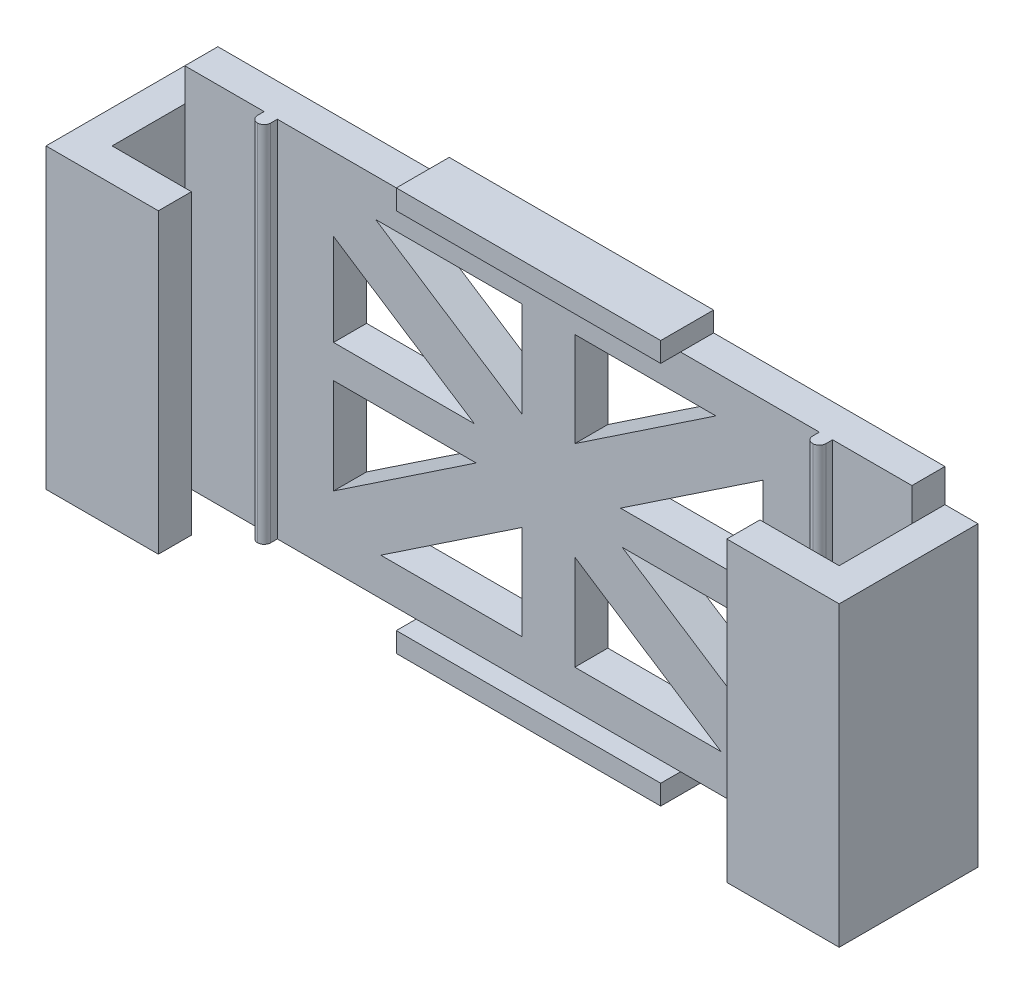
SolidWorks part; units mm, degrees
ref_plane "Front Plane" through (0, 0, 0) normal (0, 0, 1) x (1, 0, 0)
ref_plane "Top Plane" through (0, 0, 0) normal (0, 1, 0) x (1, 0, 0)
ref_plane "Right Plane" through (0, 0, 0) normal (1, 0, 0) x (0, 0, -1)
sketch "Sketch1" plane through (0, 0, 0) normal (0, 0, 1) x (1, 0, 0)
  line L0 (0, -36.5349) -> (0, 35.9982) construction
  line L1 (-55, -27.5) -> (55, -27.5)
  line L2 (-55, -27.5) -> (-55, 27.5)
  line L3 (-55, 27.5) -> (55, 27.5)
  line L4 (55, -27.5) -> (55, 27.5)
  line L5 (-55, -27.5) -> (55, 27.5) construction
  line L6 (-55, 27.5) -> (55, -27.5) construction
  line L11 (-43, -27.5) -> (-41, -27.5)
  line L12 (-43, -27.5) -> (-43, 27.5)
  line L13 (-43, 27.5) -> (-41, 27.5)
  line L14 (-41, -27.5) -> (-41, 27.5)
  line L15 (55, 27.5) -> (43, 27.5)
  line L16 (43, -27.5) -> (43, 27.5)
  line L17 (55, -27.5) -> (43, -27.5)
  line L18 (55, -27.5) -> (55, 27.5)
  line L19 (43, 27.5) -> (41, 27.5)
  line L20 (41, -27.5) -> (41, 27.5)
  line L21 (43, -27.5) -> (41, -27.5)
  line L22 (43, -27.5) -> (43, 27.5)
  point P0 (0, 0)
  dimension "D1" = 55
  dimension "D2" = 110
  dimension "D3" = 12
  dimension "D4" = 2
extrude "Boss-Extrude1" add sketch "Sketch1" along normal blind 5 contours L1 L20 L3 L14 | L1 L12 L3 L2 | L16 L1 L4 L3 region at (-49, 0, 0) region at (0, 0, 0) region at (49, 0, 0)
extrude "Boss-Extrude2" add sketch "Sketch1<3>" along normal blind 7 contours L20 L1 L16 L3 | L12 L13 L14 L11 region at (42, 0, 0)
sketch "Sketch1<3>" plane through (0, 0, 0) normal (0, 0, 1) x (1, 0, 0) same geometry as "Sketch1"
fillet "Fillet1" radius 1 4 edges at (-43, 0, 7) (-41, 0, 7) (41, 0, 7) (43, 0, 7)
sketch "Sketch2" plane through (0, 0, 0) normal (0, 0, 1) x (1, 0, 0)
  line L0 (-55, -27.5) -> (-55, 27.5) construction
  line L1 (-55, 22.5) -> (-60, 22.5)
  line L2 (-55, 22.5) -> (-55, -22.5)
  line L3 (-55, -22.5) -> (-60, -22.5)
  line L4 (-60, 22.5) -> (-60, -22.5)
  line L5 (-55, -27.5) -> (-43, -27.5) construction
  line L6 (-55, 27.5) -> (-43, 27.5) construction
  line L7 (0, -33.0129) -> (0, 33.9612) construction
  line L8 (55, -22.5) -> (60, -22.5)
  line L9 (60, 22.5) -> (60, -22.5)
  line L10 (55, 22.5) -> (60, 22.5)
  line L11 (55, 22.5) -> (55, -22.5)
  dimension "D1" = 5
  dimension "D2" = 5
  dimension "D3" = 5
extrude "Boss-Extrude3" add sketch "Sketch2" along normal blind 16
ref_plane "Plane1" through (0, 0, 16) normal (0, 0, 1) x (1, 0, 0)
sketch "Sketch3" plane through (0, 0, 16) normal (0, 0, 1) x (1, 0, 0)
  line L0 (0, 0) -> (0, -34.1454) construction
  line L1 (60, -22.5) -> (43, -22.5)
  line L2 (60, -22.5) -> (60, 22.5)
  line L3 (60, 22.5) -> (43, 22.5)
  line L4 (43, -22.5) -> (43, 22.5)
  line L5 (-60, 22.5) -> (-43, 22.5)
  line L6 (-43, -22.5) -> (-43, 22.5)
  line L7 (-60, -22.5) -> (-43, -22.5)
  line L8 (-60, -22.5) -> (-60, 22.5)
  dimension "D1" = 45
  dimension "D2" = 17
extrude "Boss-Extrude4" add sketch "Sketch3" along normal blind 5
sketch "Sketch4" plane through (0, 0, 0) normal (0, 0, 1) x (1, 0, 0)
  line L0 (-41, -27.5) -> (41, -27.5) construction
  line L1 (-20, -27.5) -> (20, -27.5)
  line L2 (0, -27.5) -> (0, -30.5)
  line L3 (-20, -30.5) -> (20, -30.5)
  line L4 (20, -27.5) -> (20, -30.5)
  line L5 (0, -13.7133) -> (0, 0) construction
  line L6 (0, 0) -> (14.001, 0) construction
  line L7 (-20, -27.5) -> (-20, -30.5)
  line L8 (-20, 27.5) -> (-20, 30.5)
  line L9 (-20, 27.5) -> (20, 27.5)
  line L10 (20, 27.5) -> (20, 30.5)
  line L11 (-20, 30.5) -> (20, 30.5)
  dimension "D1" = 3
  dimension "D2" = 20
extrude "Boss-Extrude5" add sketch "Sketch4" along normal blind 8 contours L4 L1 L2 L3 | L3 L4 L1 L7 | L9 L10 L11 L8 region at (10, -29, 0)
sketch "Sketch5" plane through (0, 0, 5) normal (0, 0, 1) x (1, 0, 0)
  line L0 (-41, 27.5) -> (41, -27.5)
  line L1 (-41, -27.5) -> (41, 27.5)
  line L2 (0, -27.5) -> (0, 27.5)
  line L3 (-20, -27.5) -> (20, -27.5) construction
  line L4 (-20, 27.5) -> (20, 27.5) construction
  line L5 (41, -27.5) -> (41, 27.5) construction
  line L6 (-41, -27.5) -> (-41, 27.5) construction
  line L7 (-41, 0) -> (41, 0)
  line L8 (41, -27.5) -> (41, 27.5) construction
  line L9 (-41, 2.5) -> (41, 2.5)
  line L10 (-41, 2.5) -> (-41, -2.5)
  line L11 (-41, -2.5) -> (41, -2.5)
  line L12 (41, 2.5) -> (41, -2.5)
  line L13 (-41, 2.5) -> (41, -2.5) construction
  line L14 (-41, -2.5) -> (41, 2.5) construction
  line L15 (-41, 21.92) -> (34.9082, -27.5)
  line L18 (-34.9082, 27.5) -> (41, -21.92)
  line L19 (-41, 22.2) -> (41, -22.2) construction
  line L20 (35.583, -27.5) -> (-35.583, 27.5) construction
  line L21 (-41, -22.6544) -> (33.8596, 27.5)
  line L24 (-33.8596, -27.5) -> (41, 22.6544)
  line L25 (-41, -22.9039) -> (41, 22.9039) construction
  line L26 (34.6299, 27.5) -> (-34.6299, -27.5) construction
  line L27 (-20, 27.5) -> (20, 27.5) construction
  line L28 (-4, -27.5) -> (4, -27.5)
  line L29 (-4, -27.5) -> (-4, 27.5)
  line L30 (-4, 27.5) -> (4, 27.5)
  line L31 (4, -27.5) -> (4, 27.5)
  line L32 (-4, -27.5) -> (4, 27.5) construction
  line L33 (-4, 27.5) -> (4, -27.5) construction
  line L35 (-41, -27.5) -> (41, -27.5)
  line L36 (-41, -27.5) -> (-41, 27.5)
  line L37 (-41, 27.5) -> (41, 27.5)
  line L38 (41, -27.5) -> (41, 27.5)
  line L39 (-41, -27.5) -> (41, 27.5) construction
  line L40 (-41, 27.5) -> (41, -27.5) construction
  line L41 (32.5, 21.7988) -> (-32.5, 21.7988)
  line L42 (32.5, 21.7988) -> (32.5, -21.7988)
  line L43 (32.5, -21.7988) -> (-32.5, -21.7988)
  line L44 (-32.5, 21.7988) -> (-32.5, -21.7988)
  line L45 (32.5, 21.7988) -> (-32.5, -21.7988) construction
  line L46 (32.5, -21.7988) -> (-32.5, 21.7988) construction
  point P20 (0, 0)
  point P28 (0, 0)
  point P29 (0, 0)
  point P30 (0, 0)
  point P36 (0, 0)
  point P45 (0, 0)
  dimension "D1" = 5
  dimension "D2" = 65
  dimension "D4" = 8
extrude "Cut-Extrude1" cut sketch "Sketch5" against normal blind 8 contours L42 L11 L18 | L43 L15 L31 | L43 L29 L24 | L11 L44 L21 | L15 L44 L9 | L29 L41 L18 | L21 L41 L31 | L42 L24 L9 region at (-11.3837, 16.9916, 5) region at (-25.3904, 7.1287, 5) region at (11.1167, 17.0307, 5) region at (-25.306, -7.3199, 5) region at (25.306, 7.3199, 5) region at (-11.1167, -17.0307, 5) region at (11.3837, -16.9916, 5) region at (25.3904, -7.1287, 5)
